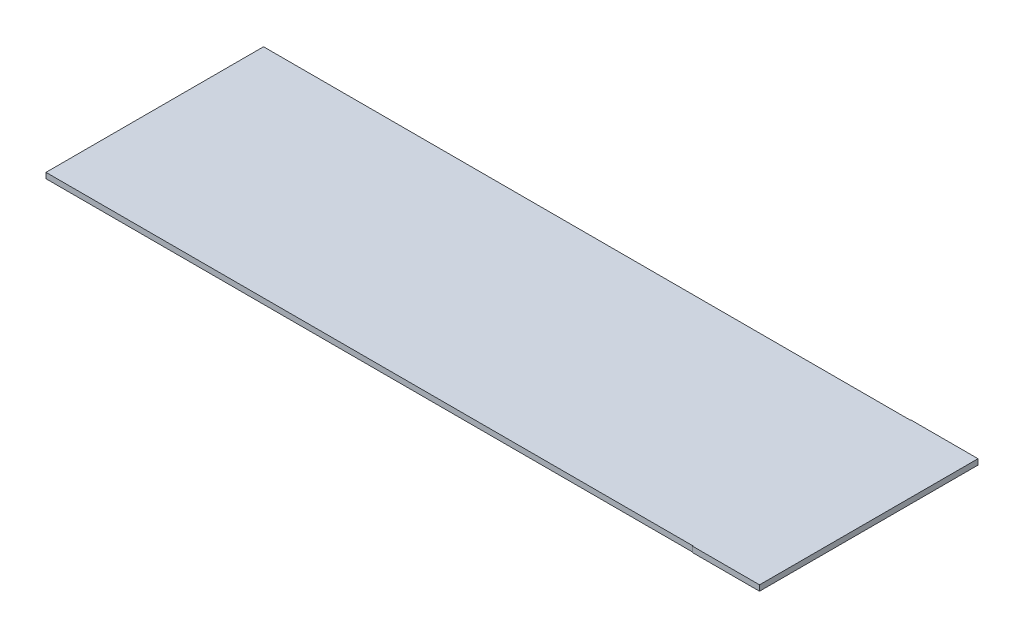
SolidWorks part; units mm, degrees
ref_plane "Front Plane" through (0, 0, 0) normal (0, 0, 1) x (1, 0, 0)
ref_plane "Top Plane" through (0, 0, 0) normal (0, 1, 0) x (1, 0, 0)
ref_plane "Right Plane" through (0, 0, 0) normal (1, 0, 0) x (0, 0, -1)
sketch "Sketch1" plane through (0, 0, 0) normal (0, 1, 0) x (1, 0, 0)
  line L0 (-203.2, 0) -> (203.2, 0) construction
  line L1 (-203.2, 62.1792) -> (203.2, 62.1792)
  line L2 (-203.2, 62.1792) -> (-203.2, -62.1792)
  line L3 (-203.2, -62.1792) -> (203.2, -62.1792)
  line L4 (203.2, 62.1792) -> (203.2, -62.1792)
  line L5 (-203.2, 62.1792) -> (203.2, -62.1792) construction
  line L6 (-203.2, -62.1792) -> (203.2, 62.1792) construction
  line L7 (-203.2, -62.1792) -> (165.1, -62.1792)
  line L8 (-203.2, -62.1792) -> (-203.2, -61.9125)
  line L9 (-203.2, -61.9125) -> (165.1, -61.9125)
  line L10 (165.1, -62.1792) -> (165.1, -61.9125)
  line L11 (-203.2, 62.1792) -> (165.1, 62.1792)
  line L12 (-203.2, 62.1792) -> (-203.2, 61.9125)
  line L13 (-203.2, 61.9125) -> (165.1, 61.9125)
  line L14 (165.1, 62.1792) -> (165.1, 61.9125)
  point P0 (0, 0)
  dimension "D1" = 406.4
  dimension "D2" = 124.3584
  dimension "D3" = 38.1
  dimension "D4" = 123.825
  dimension "D5" = 61.9125
extrude "Boss-Extrude1" add sketch "Sketch1" along normal mid plane 3.175 contours L1 L14 L13 L2 L9 L10 L3 L4 region at (0.0743, 0, 0)
equation "\"D2@Sketch1\"=4.90-0.004"
equation "\"D1@Sketch1\"=16.00in"
equation "\"D3@Sketch1\"=1.50in"
equation "\"D5@Sketch1\"=4.875/2"
